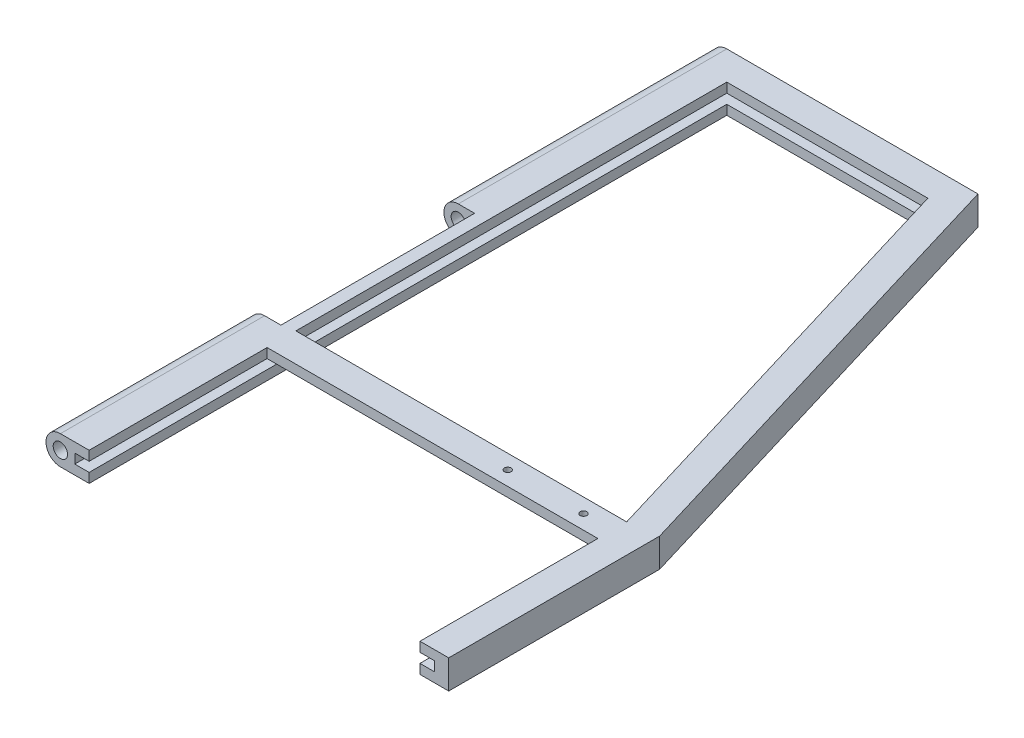
SolidWorks part; units mm, degrees
ref_plane "前视基准面" through (0, 0, 0) normal (0, 0, 1) x (1, 0, 0)
ref_plane "上视基准面" through (0, 0, 0) normal (0, 1, 0) x (1, 0, 0)
ref_plane "右视基准面" through (0, 0, 0) normal (1, 0, 0) x (0, 0, -1)
other "Configuration Table"
sketch "草图1" plane through (0, 0, 0) normal (0, 1, 0) x (1, 0, 0)
  line L0 (0, 0) -> (0, -73)
  line L1 (0, -73) -> (38.8, -73)
  line L2 (38.8, -73) -> (38.8, -47.5)
  line L3 (38.8, -47.5) -> (24.5, 0)
  line L4 (24.5, 0) -> (0, 0)
  dimension "D3" = 25.5
  dimension "D4" = 24.5
  dimension "D1" = 73
  dimension "D2" = 38.8
extrude "凸台-拉伸1" add sketch "草图1" along normal blind 3
sketch "草图2" plane through (0, 0, 0) normal (0, 0, -1) x (-1, 0, 0)
  line L0 (0.2, 0) -> (0.2, 3) construction
  line L1 (0, 0) -> (1.7, 0)
  line L2 (0, 0) -> (0, 3)
  line L3 (0, 3) -> (1.7, 3)
  line L4 (1.7, 0) -> (1.7, 3) construction
  circle A0 centre (1.7, 1.5) radius 1.5
  circle A1 centre (1.7, 1.5) radius 0.75
  line M10 (0, 0) -> (0, 3)
  dimension "D2" = 1.5
  dimension "D1" = 0.2
extrude "凸台-拉伸2" add sketch "草图2" against normal up to surface (73 mm away) contours A0 L3 L1 M10 | A0 A1 region at (-0.0345, 1.5, 0) region at (-0.2424, 1.5, 0) up to face at (19.4, 1.5, 73)
sketch "草图3" plane through (0, 3, 0) normal (0, 1, 0) x (1, 0, 0)
  line L0 (-1.7, -73) -> (38.8, -73) construction
  line L1 (38.8, -73) -> (-3.2, -73)
  line L2 (38.8, -73) -> (38.8, -69.5)
  line L3 (38.8, -69.5) -> (-3.2, -69.5)
  line L4 (-3.2, -73) -> (-3.2, -69.5)
  line L5 (38.8, -73) -> (38.8, -47.5) construction
  line L6 (-3.2, 0) -> (-3.2, -73) construction
  line L7 (-1.7, -73) -> (-1.7, 0) construction
  line L8 (0, -48.2) -> (-3.2, -48.2)
  line L9 (0, -48.2) -> (0, -28)
  line L10 (0, -28) -> (-3.2, -28)
  line L11 (-3.2, -48.2) -> (-3.2, -28)
  line L12 (-1.7, 0) -> (-3.2, 0) construction
  line L13 (1.3, -3) -> (22.2702, -3)
  line L14 (22.2702, -3) -> (35.8, -47.9418)
  line L15 (35.8, -47.9418) -> (35.8, -69.5)
  line L16 (35.8, -69.5) -> (1.3, -69.5)
  line L17 (1.3, -69.5) -> (1.3, -3)
  line L18 (38.8, -47.5) -> (24.5, 0) construction
  line L19 (24.5, 0) -> (-1.7, 0) construction
  dimension "D1" = 3.5
  dimension "D2" = 20.2
  dimension "D3" = 28
  dimension "D4" = 3
  dimension "D5" = 3
  dimension "D6" = 3
  dimension "D7" = 3
  dimension "D8" = 3.2
extrude "切除-拉伸1" cut sketch "草图3" against normal through all contours L17 L3 L15 L14 L13 | L11 L10 L9 L8 | L3 L4 L1 L2 region at (16.6038, 3, 39.0408)
sketch "草图4" plane through (1.3, 0, 0) normal (1, 0, 0) x (0, 0, -1)
  line L0 (-69.5, 0) -> (-69.5, 3) construction
  line L1 (-1.5, 1) -> (-69.5, 1)
  line L2 (-1.5, 1) -> (-1.5, 2)
  line L3 (-1.5, 2) -> (-69.5, 2)
  line L4 (-69.5, 1) -> (-69.5, 2)
  line L5 (-69.5, 0) -> (-47.5, 0) construction
  line L6 (-3, 0) -> (-3, 3) construction
  line L7 (-47.5, 2) -> (-47.5, 1)
  line L8 (-47.5, 3) -> (-47.5, 0) construction
  line M5 (-69.5, 3) -> (-69.5, 0)
  line M7 (-3, 0) -> (-3, 3)
  dimension "D1" = 1
  dimension "D2" = 1
  dimension "D3" = 1.5
extrude "切除-拉伸2" cut sketch "草图4" along normal offset from surface (24.0367 mm away) 1.5 from offset 1.5 contours L3 L7 L1 M7 region at (1.3, 1.5, 25.25) up to face at (29.0351, 1.5, 25.4709) offset beyond the face yes offset against normal yes
extrude "切除-拉伸3" cut sketch "草图4<3>" along normal offset from surface (37.5 mm away) 1.5 from offset 1.5 contours L7 L3 L1 M5 region at (1.3, 1.5, 58.5) up to face at (35.8, 1.5, 58.7209) offset beyond the face yes offset against normal yes
sketch "草图4<3>" plane through (1.3, 0, 0) normal (1, 0, 0) x (0, 0, -1) same geometry as "草图4"
sketch "草图5" plane through (35.8, 0, 0) normal (-1, 0, 0) x (0, 0, 1)
  line L0 (47.9418, 3) -> (69.5, 3) construction
  line L1 (47.9418, 3) -> (50.9418, 3)
  line L2 (47.9418, 3) -> (47.9418, 2)
  line L3 (47.9418, 2) -> (50.9418, 2)
  line L4 (50.9418, 3) -> (50.9418, 2)
  line L5 (47.9418, 2) -> (69.5, 2) construction
  line L6 (47.9418, 2) -> (47.9418, 3) construction
  dimension "D1" = 3
extrude "凸台-拉伸3" add sketch "草图5" along normal up to surface (34.5 mm away) up to face at (1.3, 2.5, 36.25)
sketch "草图6" plane through (0, 3, 0) normal (0, 1, 0) x (1, 0, 0)
  line L0 (35.8, -50.9418) -> (35.8, -47.9418) construction
  line L1 (35.8, -50.9418) -> (35.8, -69.5) construction
  line L2 (1.3, -50.9418) -> (35.8, -50.9418) construction
  line L3 (1.3, -47.9418) -> (35.8, -47.9418) construction
  circle A0 centre (32.8, -49.4418) radius 0.35
  circle A1 centre (24.9, -49.4418) radius 0.35
  point P14 (35.8, -49.4418)
  dimension "D1" = 0.7
  dimension "D2" = 7.9
  dimension "D3" = 3
extrude "切除-拉伸4" cut sketch "草图6" against normal through all
sketch "草图7" plane through (0, 0, 3) normal (0, 0, 1) x (1, 0, 0)
  line L0 (-0.2, 2) -> (-0.2, 1) construction
  line L1 (-0.2, 2) -> (23.8367, 2)
  line L2 (-0.2, 2) -> (-0.2, 1)
  line L3 (-0.2, 1) -> (23.8367, 1)
  line L4 (23.8367, 2) -> (23.8367, 1)
  line L5 (22.2702, 1) -> (35.8, 1) construction
  line L6 (1.3, 2) -> (35.8, 2) construction
  line L7 (23.8367, 2) -> (23.8367, 1) construction
  point P8 (0, 0)
  point P11 (21.3483, 1)
extrude "切除-拉伸5" cut sketch "草图7" against normal blind 1.5
